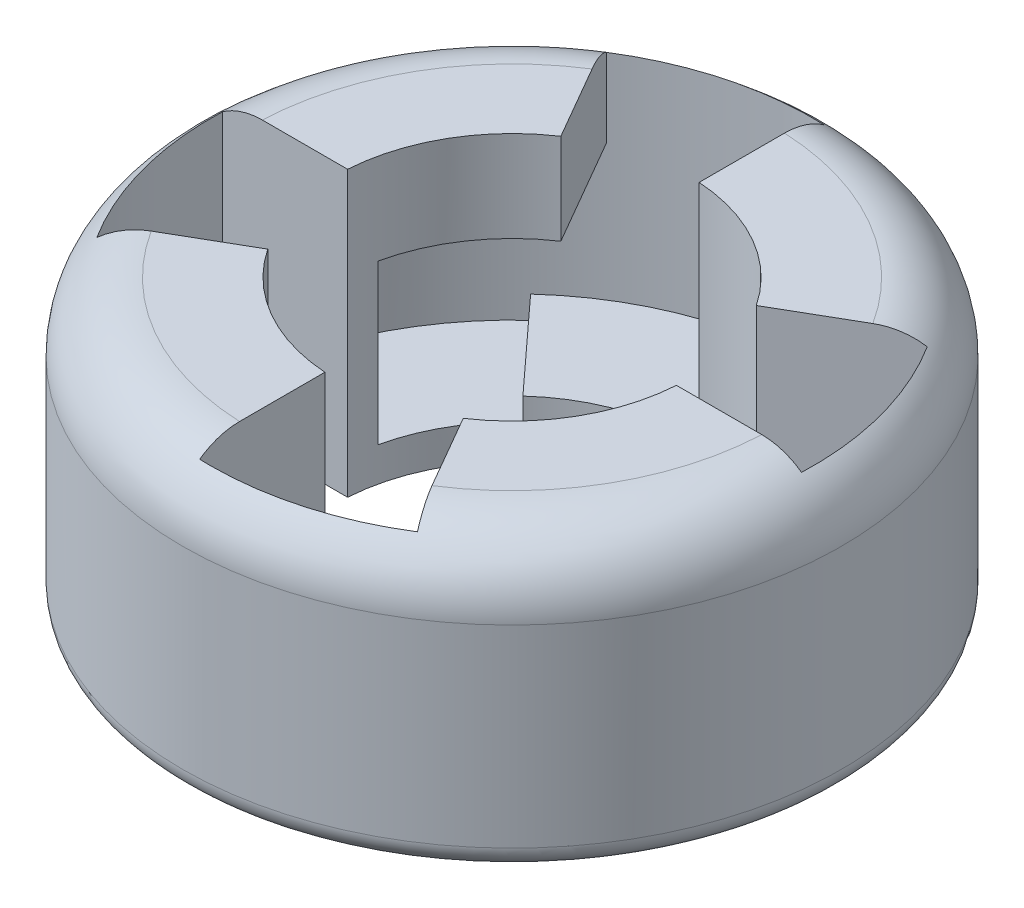
SolidWorks part; units mm, degrees
ref_plane "Front Plane" through (0, 0, 0) normal (0, 0, 1) x (1, 0, 0)
ref_plane "Top Plane" through (0, 0, 0) normal (0, 1, 0) x (1, 0, 0)
ref_plane "Right Plane" through (0, 0, 0) normal (1, 0, 0) x (0, 0, -1)
sketch "Sketch2" plane through (0, 0, 0) normal (1, 0, 0) x (0, 0, -1)
  line L0 (-7.75, 0) -> (-14.5, 0)
  line L1 (-14.5, 0) -> (-14.5, 12.5)
  line L3 (0, 31) -> (0, 21) construction
  line L6 (-14.5, 12.5) -> (-7.75, 12.5)
  line L7 (-7.75, 12.5) -> (-7.75, 0)
  dimension "D1" = 14.5
  dimension "D2" = 7.75
  dimension "D3" = 12.5
revolve "Revolve1" add sketch "Sketch2" angle 360 about L3
sketch "Sketch3" plane through (0, 12.5, 0) normal (0, 1, 0) x (1, 0, 0)
  line L2 (-6.375, 11.0418) -> (0, 0) construction
  line L5 (0, 12.75) -> (0, 0) construction
  line L6 (-7.0533, 11.2167) -> (0.5, -1.866)
  line L7 (0.5, 13.2406) -> (0.5, -1.866)
  arc A0 (0.5, 13.2406) -> (-7.0533, 11.2167) centre (0, 0) ccw
  arc A1 (0, 12.75) -> (-6.375, 11.0418) centre (0, 0) ccw construction
  dimension "D2" = 12.75
  dimension "D1" = 30
  dimension "D3" = 0.5
extrude "Cut-Extrude1" cut sketch "Sketch3" against normal blind 10
pattern_circular "CirPattern1" count 4 over 360 about axis through (0, 12.5, 0) along (0, 1, 0) of "Cut-Extrude1"
sketch "Sketch4" plane through (0, 2.5, 0) normal (0, 1, 0) x (1, 0, 0)
  line L5 (-7.7339, 0.5) -> (-13.2406, 0.5)
  line L6 (-11.2167, -7.0533) -> (-6.4477, -4.2999)
  line L7 (-7.7339, 0.5) -> (-13.2406, 0.5)
  line L8 (-11.2167, -7.0533) -> (-6.4477, -4.2999)
  arc A5 (-13.2406, 0.5) -> (-11.2167, -7.0533) centre (0, 0) ccw
  arc A6 (-7.7339, 0.5) -> (-6.4477, -4.2999) centre (0, 0) ccw
  arc A7 (-13.2406, 0.5) -> (-11.2167, -7.0533) centre (0, 0) ccw
  arc A8 (-7.7339, 0.5) -> (-6.4477, -4.2999) centre (0, 0) ccw
  dimension "D1" = 0
extrude "Cut-Extrude2" cut sketch "Sketch4" against normal blind 10
sketch "Sketch5" plane through (0, 2.5, 0) normal (0, 1, 0) x (1, 0, 0)
  line L0 (0, 0) -> (-8.9516, 9.7689)
  line L1 (0, 0) -> (-12.9359, 2.8678)
  line L4 (0, 0) -> (-11.4748, 6.625) construction
  line L5 (0, 0) -> (0, 4.0192) construction
  arc A0 (-8.9516, 9.7689) -> (-12.9359, 2.8678) centre (0, 0) ccw
  arc A1 (0.5, 13.2406) -> (-7.0533, 11.2167) centre (0, 0) ccw construction
  dimension "D1" = 35
  dimension "D2" = 60
extrude "Cut-Extrude3" cut sketch "Sketch5" along normal blind 6 and the other way blind 1
fillet "Fillet1" radius 3 1 edges at (0, 12.5, 14.5)
sketch "Sketch8" plane through (0, 2.5, 0) normal (0, 1, 0) x (1, 0, 0)
  line L0 (-4.2999, 6.4477) -> (-7.0533, 11.2167)
  line L1 (-5.2358, 5.7139) -> (-8.9516, 9.7689)
  arc A0 (-4.2999, 6.4477) -> (-5.2358, 5.7139) centre (0, 0) ccw
  arc A1 (-7.0533, 11.2167) -> (-8.9516, 9.7689) centre (0, 0) ccw
  arc A4 (0.5, 13.2406) -> (-7.0533, 11.2167) centre (0, 0) ccw construction
  arc A5 (0.5, 7.7339) -> (-4.2999, 6.4477) centre (0, 0) ccw construction
extrude "Cut-Extrude5" cut sketch "Sketch8" along normal blind 6
pattern_circular "CirPattern2" count 2 over 360 about axis through (0, 12.5, 0) along (0, 1, 0) of "Cut-Extrude3", "Cut-Extrude5", "Cut-Extrude2"
fillet "Fillet2" radius 1 1 edges at (0, 0, 14.5)
